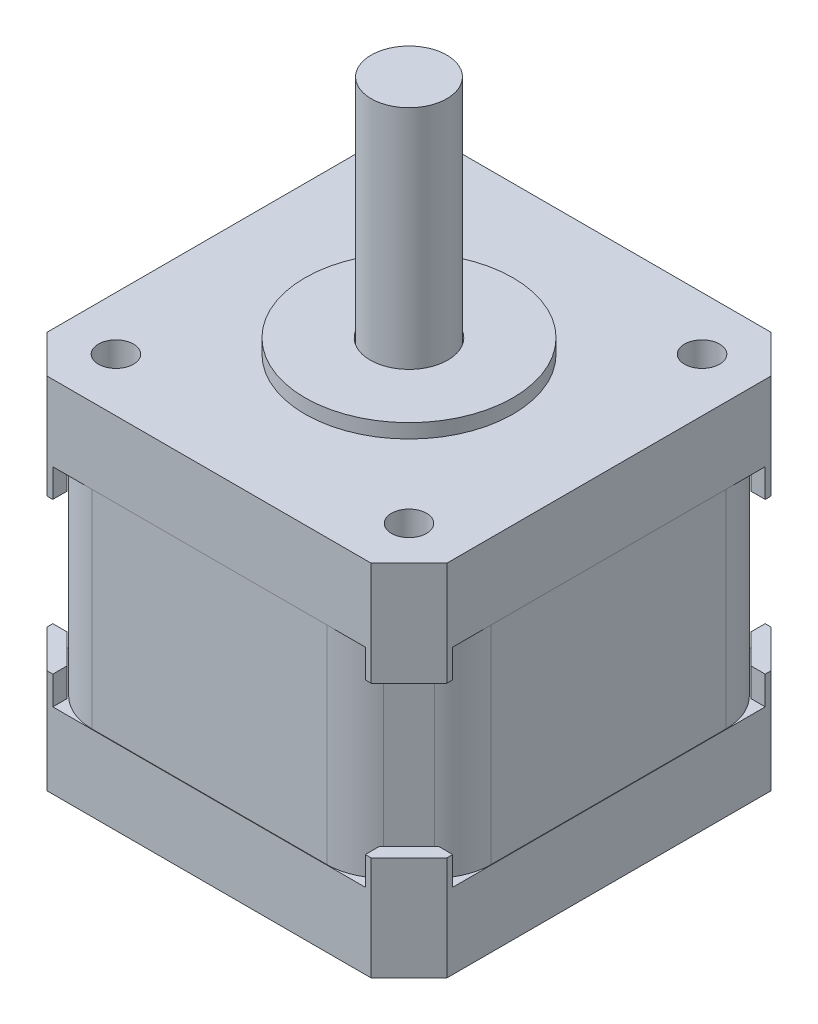
SolidWorks part; units mm, degrees
ref_plane "Plano frontal" through (0, 0, 0) normal (0, 0, 1) x (1, 0, 0)
ref_plane "Plano superior" through (0, 0, 0) normal (0, 1, 0) x (1, 0, 0)
ref_plane "Plano direito" through (0, 0, 0) normal (1, 0, 0) x (0, 0, -1)
sketch "Esboço1" plane through (0, 0, 0) normal (0, 1, 0) x (1, 0, 0)
  line L1 (-21.15, 21.15) -> (21.15, 21.15)
  line L2 (-21.15, 21.15) -> (-21.15, -21.15)
  line L3 (-21.15, -21.15) -> (21.15, -21.15)
  line L4 (21.15, 21.15) -> (21.15, -21.15)
  line L5 (-21.15, 21.15) -> (21.15, -21.15) construction
  line L6 (-21.15, -21.15) -> (21.15, 21.15) construction
  point P0 (0, 0)
  dimension "D1" = 42.3
  dimension "D2" = 42.3
extrude "UpperBody" add sketch "Esboço1" along normal blind 8
chamfer "Chanfro1" distance 4 angle 45 4 edges at (-21.15, 4, 21.15) (21.15, 4, -21.15) (-21.15, 4, -21.15) (21.15, 4, 21.15)
sketch "Esboço2" plane through (0, 8, 0) normal (0, 1, 0) x (1, 0, 0)
  circle A0 centre (0, 0) radius 11
  circle A1 centre (0, 0) radius 4.1
  dimension "D1" = 22
  dimension "D2" = 8.2
extrude "LittleTopCircle" add sketch "Esboço2" along normal blind 1.5
sketch "Esboço3" plane through (0, 8, 0) normal (0, 1, 0) x (1, 0, 0)
  line L0 (0, 21.15) -> (0, -21.15) construction
  line L1 (17.15, 21.15) -> (-17.15, 21.15) construction
  line L2 (-17.15, -21.15) -> (17.15, -21.15) construction
  line L3 (-21.15, 0) -> (21.15, 0) construction
  line L4 (-21.15, 17.15) -> (-21.15, -17.15) construction
  line L5 (21.15, -17.15) -> (21.15, 17.15) construction
  circle A0 centre (-15.5, 15.5) radius 1.8537
  dimension "D1" = 15.5
  dimension "D2" = 15.5
extrude "MountingHoles" cut sketch "Esboço3" against normal blind 25
pattern_circular "PadrãoCircular1" count 4 over 360 about axis through (0, 8, 0) along (0, 1, 0) of "MountingHoles"
sketch "Esboço7" plane through (0, 0, 0) normal (0, -1, 0) x (1, 0, 0)
  line L8 (-21.15, -16.5287) -> (-19.65, -16.5287)
  line L9 (-21.15, -17.15) -> (-21.15, 17.15) construction
  line L10 (-16.5287, -21.15) -> (-16.5287, -19.65)
  line L11 (17.15, -21.15) -> (-17.15, -21.15) construction
  line L16 (-16.5287, -19.65) -> (16.5287, -19.65)
  line L17 (16.5287, -19.65) -> (19.65, -16.5287)
  line L18 (19.65, -16.5287) -> (19.65, 16.5287)
  line L19 (19.65, 16.5287) -> (16.5287, 19.65)
  line L20 (16.5287, 19.65) -> (-16.5287, 19.65)
  line L21 (-16.5287, 19.65) -> (-19.65, 16.5287)
  line L22 (-19.65, 16.5287) -> (-19.65, -16.5287)
  line L23 (-19.65, -16.5287) -> (-16.5287, -19.65)
  line L24 (-16.5287, -19.65) -> (16.5287, -19.65)
  line L25 (16.5287, -19.65) -> (19.65, -16.5287)
  line L26 (19.65, -16.5287) -> (19.65, 16.5287)
  line L27 (19.65, 16.5287) -> (16.5287, 19.65)
  line L28 (16.5287, 19.65) -> (-16.5287, 19.65)
  line L29 (-16.5287, 19.65) -> (-19.65, 16.5287)
  line L30 (-19.65, 16.5287) -> (-19.65, -16.5287)
  line L31 (-19.65, -16.5287) -> (-16.5287, -19.65)
  line M13 (-17.15, -21.15) -> (17.15, -21.15)
  line M19 (-21.15, 17.15) -> (-21.15, -17.15)
  line M20 (-21.15, -17.15) -> (-17.15, -21.15)
  dimension "D1" = 1.5
extrude "LittleMetalTabs" add sketch "Esboço7" along normal blind 3 contours L31 L30 L8 L10 L24 M19 M20 M13 region at (-18.6471, 0, -18.6471)
pattern_circular "PadrãoCircular2" count 4 over 360 about axis through (0, 9.5, 0) along (0, 1, 0) of "LittleMetalTabs"
sketch "Esboço8" plane through (0, 0, 0) normal (0, -1, 0) x (1, 0, 0)
  line L4 (-14.9, 21.1) -> (14.9, 21.1)
  line L5 (-21.1, 14.9) -> (-21.1, -14.9)
  line L6 (-14.9, -21.1) -> (14.9, -21.1)
  line L7 (21.1, 14.9) -> (21.1, -14.9)
  line L8 (-21.1, 21.1) -> (21.1, -21.1) construction
  line L9 (-21.1, -21.1) -> (21.1, 21.1) construction
  line L10 (-21.1, -14.9) -> (-14.9, -21.1)
  line L11 (-21.1, 14.9) -> (-14.9, 21.1)
  line L12 (14.9, -21.1) -> (21.1, -14.9)
  line L13 (14.9, 21.1) -> (21.1, 14.9)
  point P4 (0, 0)
  dimension "D1" = 42.2
  dimension "D2" = 42.2
extrude "MiddleBody" add sketch "Esboço8" along normal blind 22
fillet "Filete1" radius 6 8 edges at (-21.1, -11, -14.9) (-21.1, -11, 14.9) (-14.9, -11, 21.1) (14.9, -11, 21.1) (-14.9, -11, -21.1) (21.1, -11, 14.9) (14.9, -11, -21.1) (21.1, -11, -14.9)
sketch "Esboço9" plane through (0, -22, 0) normal (0, -1, 0) x (1, 0, 0)
  line L1 (-21.15, -21.15) -> (21.15, -21.15)
  line L2 (-21.15, -21.15) -> (-21.15, 21.15)
  line L3 (-21.15, 21.15) -> (21.15, 21.15)
  line L4 (21.15, -21.15) -> (21.15, 21.15)
  line L5 (-21.15, -21.15) -> (21.15, 21.15) construction
  line L6 (-21.15, 21.15) -> (21.15, -21.15) construction
  point P0 (0, 0)
  dimension "D1" = 42.3
  dimension "D2" = 42.3
extrude "BottomBody" add sketch "Esboço9" along normal blind 8
chamfer "Chanfro5" distance 4 angle 45 4 edges at (21.15, -26, 21.15) (21.15, -26, -21.15) (-21.15, -26, 21.15) (-21.15, -26, -21.15)
sketch "Esboço10" plane through (0, -22, 0) normal (0, 1, 0) x (1, 0, 0)
  line L0 (-16.5287, -19.65) -> (-16.5287, -21.15)
  line L1 (17.15, -21.15) -> (-17.15, -21.15) construction
  line L2 (-19.65, -16.5287) -> (-21.15, -16.5287)
  line L3 (-21.15, -17.15) -> (-21.15, 17.15) construction
  line L16 (-16.5287, -19.65) -> (16.5287, -19.65)
  line L17 (16.5287, -19.65) -> (19.65, -16.5287)
  line L18 (19.65, -16.5287) -> (19.65, 16.5287)
  line L19 (19.65, 16.5287) -> (16.5287, 19.65)
  line L20 (16.5287, 19.65) -> (-16.5287, 19.65)
  line L21 (-16.5287, 19.65) -> (-19.65, 16.5287)
  line L22 (-19.65, 16.5287) -> (-19.65, -16.5287)
  line L23 (-19.65, -16.5287) -> (-16.5287, -19.65)
  line L24 (-16.5287, -19.65) -> (16.5287, -19.65)
  line L25 (16.5287, -19.65) -> (19.65, -16.5287)
  line L26 (19.65, -16.5287) -> (19.65, 16.5287)
  line L27 (19.65, 16.5287) -> (16.5287, 19.65)
  line L28 (16.5287, 19.65) -> (-16.5287, 19.65)
  line L29 (-16.5287, 19.65) -> (-19.65, 16.5287)
  line L30 (-19.65, 16.5287) -> (-19.65, -16.5287)
  line L31 (-19.65, -16.5287) -> (-16.5287, -19.65)
  line M9 (-17.15, -21.15) -> (17.15, -21.15)
  line M15 (-21.15, 17.15) -> (-21.15, -17.15)
  line M16 (-21.15, -17.15) -> (-17.15, -21.15)
  dimension "D1" = 1.5
extrude "LittleMetalTabs2" add sketch "Esboço10" along normal blind 3 contours L31 L2 L0 M15 M16 M9 region at (-18.6471, -22, 18.6471)
ref_point "Ponto2"
ref_axis "Eixo1" through (0, -30, 0) along (0, 1, 0)
pattern_circular "PadrãoCircular3" count 4 over 360 about axis through (0, -30, 0) along (0, 1, 0) of "LittleMetalTabs2"
sketch "Esboço4" plane through (0, 8, 0) normal (0, 1, 0) x (1, 0, 0)
  circle A0 centre (0, 0) radius 4
  dimension "D1" = 8
ref_point "Ponto1"
extrude "Boss-Extrude1" add sketch "Esboço4" along normal blind 25.4 contours A0
